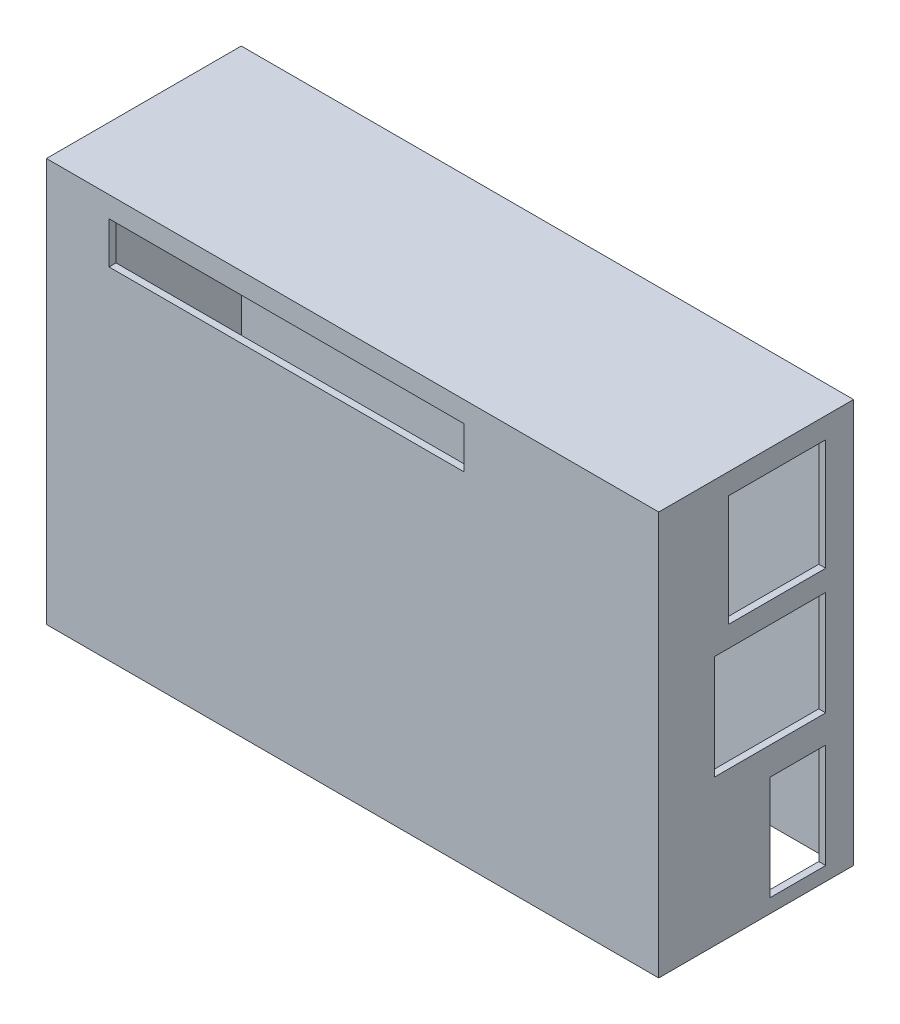
SolidWorks part; units mm, degrees
ref_plane "前视基准面" through (0, 0, 0) normal (0, 0, 1) x (1, 0, 0)
ref_plane "上视基准面" through (0, 0, 0) normal (0, 1, 0) x (1, 0, 0)
ref_plane "右视基准面" through (0, 0, 0) normal (1, 0, 0) x (0, 0, -1)
sketch "草图1" plane through (0, 0, 0) normal (0, 0, 1) x (1, 0, 0)
  line L1 (-38.2657, 24.0983) -> (49.7343, 24.0983)
  line L2 (-38.2657, 24.0983) -> (-38.2657, -33.9017)
  line L3 (-38.2657, -33.9017) -> (49.7343, -33.9017)
  line L4 (49.7343, 24.0983) -> (49.7343, -33.9017)
  dimension "D1" = 88
  dimension "D2" = 58
extrude "凸台-拉伸1" add sketch "草图1" along normal blind 28
sketch "草图2" plane through (-38.2657, 0, 0) normal (-1, 0, 0) x (0, 0, 1)
  line L0 (28, 24.0983) -> (0, 24.0983) construction
  line L1 (1, 23.0983) -> (27, 23.0983)
  line L2 (1, 23.0983) -> (1, -32.9017)
  line L3 (1, -32.9017) -> (27, -32.9017)
  line L4 (27, 23.0983) -> (27, -32.9017)
  line L5 (0, 24.0983) -> (0, -33.9017) construction
  line L6 (28, 24.0983) -> (28, -33.9017) construction
  line L7 (28, -33.9017) -> (0, -33.9017) construction
  dimension "D1" = 1
  dimension "D2" = 1
  dimension "D3" = 1
  dimension "D4" = 1
extrude "切除-拉伸1" cut sketch "草图2" against normal blind 87
sketch "草图3" plane through (49.7343, 0, 0) normal (1, 0, 0) x (0, 0, -1)
  line L0 (0, -33.9017) -> (0, 24.0983) construction
  line L1 (-4, -31.9017) -> (-12, -31.9017)
  line L2 (-4, -31.9017) -> (-4, -16.9017)
  line L3 (-4, -16.9017) -> (-12, -16.9017)
  line L4 (-12, -31.9017) -> (-12, -16.9017)
  line L5 (-4, -12.9017) -> (-20, -12.9017)
  line L6 (-4, -12.9017) -> (-4, 2.0983)
  line L7 (-4, 2.0983) -> (-20, 2.0983)
  line L8 (-20, -12.9017) -> (-20, 2.0983)
  line L9 (-4, 5.0983) -> (-18, 5.0983)
  line L10 (-4, 5.0983) -> (-4, 21.0983)
  line L11 (-4, 21.0983) -> (-18, 21.0983)
  line L12 (-18, 5.0983) -> (-18, 21.0983)
  line L13 (-28, -33.9017) -> (0, -33.9017) construction
  dimension "D1" = 4
  dimension "D2" = 4
  dimension "D3" = 4
  dimension "D4" = 2
  dimension "D5" = 15
  dimension "D6" = 8
  dimension "D7" = 4
  dimension "D8" = 15
  dimension "D9" = 16
  dimension "D10" = 3
  dimension "D11" = 16
  dimension "D12" = 14
extrude "切除-拉伸2" cut sketch "草图3" against normal blind 87
sketch "草图4" plane through (-38.2657, 0, 0) normal (-1, 0, 0) x (0, 0, 1)
  line L1 (0, 24.0983) -> (28, 24.0983)
  line L2 (0, 24.0983) -> (0, -33.9017)
  line L3 (0, -33.9017) -> (28, -33.9017)
  line L4 (28, 24.0983) -> (28, -33.9017)
extrude "凸台-拉伸2" add sketch "草图4" against normal blind 1
sketch "草图6" plane through (0, 0, 28) normal (0, 0, 1) x (1, 0, 0)
  line L0 (49.7343, 24.0983) -> (-38.2657, 24.0983) construction
  line L1 (-29.2657, 21.0983) -> (21.7343, 21.0983)
  line L2 (-29.2657, 21.0983) -> (-29.2657, 15.0983)
  line L3 (-29.2657, 15.0983) -> (21.7343, 15.0983)
  line L4 (21.7343, 21.0983) -> (21.7343, 15.0983)
  line L5 (-38.2657, 24.0983) -> (-38.2657, -33.9017) construction
  dimension "D1" = 3
  dimension "D2" = 51
  dimension "D3" = 6
  dimension "D4" = 9
extrude "切除-拉伸4" cut sketch "草图6" against normal blind 10
sketch "草图7" plane through (-38.2657, 0, 0) normal (-1, 0, 0) x (0, 0, 1)
  line L0 (28, 24.0983) -> (0, 24.0983) construction
  line L1 (3, 17.0983) -> (8, 17.0983)
  line L2 (3, 17.0983) -> (3, 8.0983)
  line L3 (3, 8.0983) -> (8, 8.0983)
  line L4 (8, 17.0983) -> (8, 8.0983)
  line L5 (0, 24.0983) -> (0, -33.9017) construction
  dimension "D1" = 7
  dimension "D2" = 9
  dimension "D3" = 3
  dimension "D4" = 5
extrude "切除-拉伸5" cut sketch "草图7" against normal blind 10
sketch "草图8" plane through (0, -33.9017, 0) normal (0, -1, 0) x (1, 0, 0)
  line L0 (-38.2657, 28) -> (-38.2657, 0) construction
  line L1 (-37.2657, 27) -> (48.7343, 27)
  line L2 (-37.2657, 27) -> (-37.2657, 1)
  line L3 (-37.2657, 1) -> (48.7343, 1)
  line L4 (48.7343, 27) -> (48.7343, 1)
  line L5 (-38.2657, 28) -> (49.7343, 28) construction
  line L6 (49.7343, 28) -> (49.7343, 0) construction
  line L7 (-38.2657, 0) -> (49.7343, 0) construction
  dimension "D1" = 1
  dimension "D2" = 1
  dimension "D3" = 1
  dimension "D4" = 1
extrude "切除-拉伸6" cut sketch "草图8" against normal blind 57
